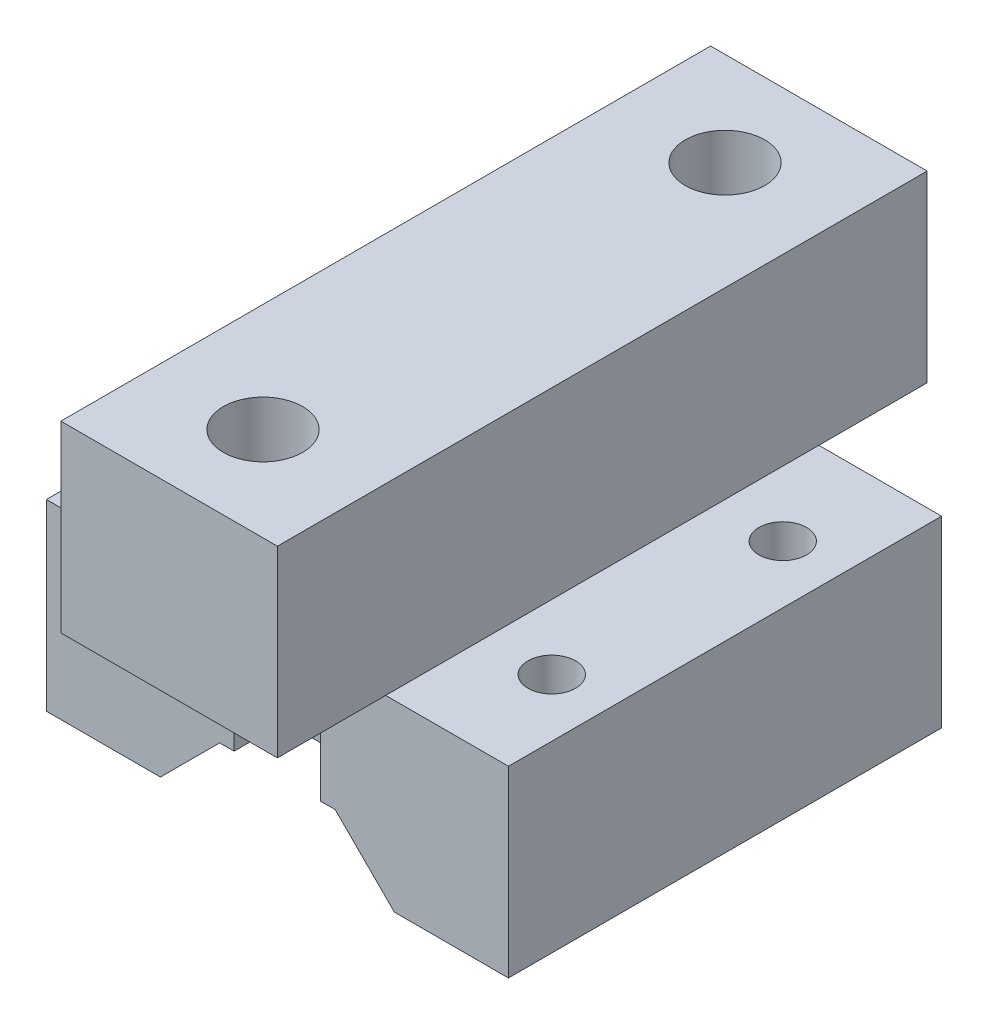
SolidWorks part; units mm, degrees
ref_plane "Front Plane" through (0, 0, 0) normal (0, 0, 1) x (1, 0, 0)
ref_plane "Top Plane" through (0, 0, 0) normal (0, 1, 0) x (1, 0, 0)
ref_plane "Right Plane" through (0, 0, 0) normal (1, 0, 0) x (0, 0, -1)
sketch "Sketch1" plane through (0, 0, 0) normal (0, 0, 1) x (1, 0, 0)
  line L0 (0, 12.1598) -> (0, -9.8313) construction
  line L1 (-4, 4.1012) -> (4, 4.1012)
  line L2 (4, 4.1012) -> (8.1012, 0)
  line L3 (8.1012, 0) -> (16, 0)
  line L4 (16, 0) -> (16, 12.7)
  line L5 (16, 12.7) -> (-16, 12.7)
  line L6 (-16, 0) -> (-16, 12.7)
  line L7 (-8.1012, 0) -> (-16, 0)
  line L8 (-4, 4.1012) -> (-8.1012, 0)
  point P3 (-12, 0)
  point P5 (12, 0)
  point P12 (0, 12.7)
  point P15 (0, 4.1012)
  dimension "D1" = 4
  dimension "D2" = 12
  dimension "D3" = 45
  dimension "D4" = 5.8
  dimension "D5" = 16
  dimension "D6" = 12.7
extrude "Boss-Extrude1" add sketch "Sketch1" along normal mid plane 30
sketch "Sketch2" plane through (0, 12.7, 0) normal (0, 1, 0) x (1, 0, 0)
  line L2 (16, 0) -> (-16, 0) construction
  circle A0 centre (12, 8) radius 1.65
  circle A1 centre (12, -8) radius 1.65
  circle A2 centre (-12, -8) radius 1.65
  circle A3 centre (-12, 8) radius 1.65
  dimension "D1" = 3.3
  dimension "D2" = 16
  dimension "D3" = 8
extrude "Cut-Extrude1" cut sketch "Sketch2" against normal up to surface (12.7 mm away) up to face at (-12.0506, 0, 0)
sketch "Sketch3" plane through (0, 12.7, 0) normal (0, 1, 0) x (1, 0, 0)
  line L0 (7.5, -22.5) -> (7.5, 22.5)
  line L1 (7.5, -22.5) -> (-7.5, -22.5)
  line L5 (3, -11.5) -> (-3, -11.5)
  line L6 (0, -22.5) -> (0, 22.5) construction
  line L7 (-7.5, -22.5) -> (-7.5, 22.5)
  line L8 (0, -55) -> (0, 55) construction
  line L9 (-7.5, 0) -> (7.5, 0) construction
  line L10 (3, -22.5) -> (-3, -22.5)
  line L11 (3, 11.5) -> (3, 22.5)
  line L13 (-3, -11.5) -> (-3, -22.5)
  line L15 (3, -11.5) -> (3, -22.5)
  line L16 (-3, 11.5) -> (-3, 22.5)
  line L17 (3, 22.5) -> (-3, 22.5)
  line L18 (3, 11.5) -> (-3, 11.5)
  line L19 (7.5, 22.5) -> (-7.5, 22.5)
  circle A0 centre (0, -16) radius 2.75
  circle A1 centre (0, 16) radius 2.75
  point P1 (0, 0)
  point P7 (0, -11.5)
  point P11 (0, 0)
  point P14 (0, -22.5)
  line M14 (16, 15) -> (-16, 15)
  line M16 (-16, -15) -> (16, -15)
  dimension "D1" = 5.5
  dimension "D2" = 22.5
  dimension "D3" = 16
  dimension "D4" = 15
  dimension "D5" = 4.5
  dimension "D6" = 6
extrude "Boss-Extrude3" add sketch "Sketch3" along normal blind 12.7 contours L0 L19 L11 M14 | L11 L18 L16 L7 L13 L5 L15 L0 M14 M16 | L16 L19 L7 M14 | A1 L11 L17 L16 M14 | A1 L16 L18 L11 M14 | A0 L13 L1 L15 M16 | L15 L1 L0 M16 | L13 L7 L1 M16 | A0 L15 L5 L13 M16 region at (5.25, 12.7, 18.75) region at (0, 12.7, 0) region at (0, 12.7, 20.0564) region at (5.25, 12.7, -18.75) region at (0, 12.7, 12.7895) region at (-5.25, 12.7, 18.75) region at (0, 12.7, -20.0564) region at (0, 12.7, -12.7895) region at (-5.25, 12.7, -18.75)
extrude "Cut-Extrude4" cut sketch "Sketch3<7>" against normal up to surface (8.5988 mm away) contours A1 L11 L17 L16 M14 | A1 L16 L18 L11 M14 | A0 L15 L5 L13 M16 | A0 L13 L1 L15 M16 | A1 | A0 region at (0, 12.7, 20.0564) region at (0, 12.7, 12.7895) region at (0, 12.7, -20.0564) region at (0, 12.7, -12.7895) up to face at (0, 4.1012, 0)
sketch "Sketch3<7>" plane through (0, 12.7, 0) normal (0, 1, 0) x (1, 0, 0) same geometry as "Sketch3"
